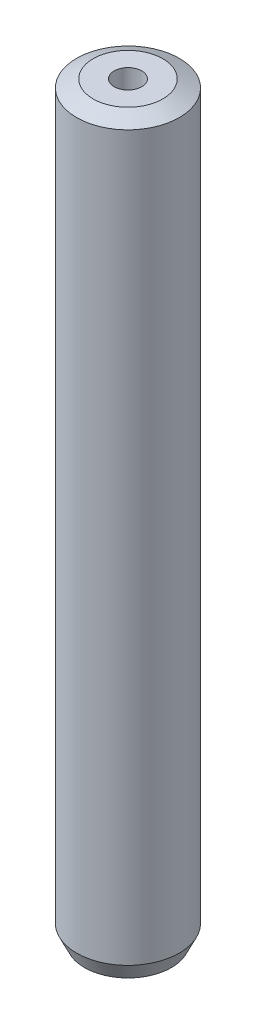
SolidWorks part; units mm, degrees
ref_plane "Front Plane" through (0, 0, 0) normal (0, 0, 1) x (1, 0, 0)
ref_plane "Top Plane" through (0, 0, 0) normal (0, 1, 0) x (1, 0, 0)
ref_plane "Right Plane" through (0, 0, 0) normal (1, 0, 0) x (0, 0, -1)
sketch "Sketch1" plane through (0, 0, 0) normal (0, 1, 0) x (1, 0, 0)
  circle A0 centre (0, 0) radius 12.5
  dimension "SHAFT_OD" = 25
extrude "Boss-Extrude1" add sketch "Sketch1" along normal blind 182.0395
sketch "Sketch2" plane through (0, 0, 0) normal (0, 1, 0) x (1, 0, 0)
  circle A0 centre (0, 0) radius 3.353
  dimension "BORE_D" = 6.7059
extrude "Cut-Extrude1" cut sketch "Sketch2" along normal through all
chamfer "Chamfer1" distance 1.9218 angle 64.452 2 edges at (0, 182.0395, 12.5) (0, 0, 12.5) first distance on face at (0, 182.0395, 12.5) first distance on face at (0, 0, 3.353)
